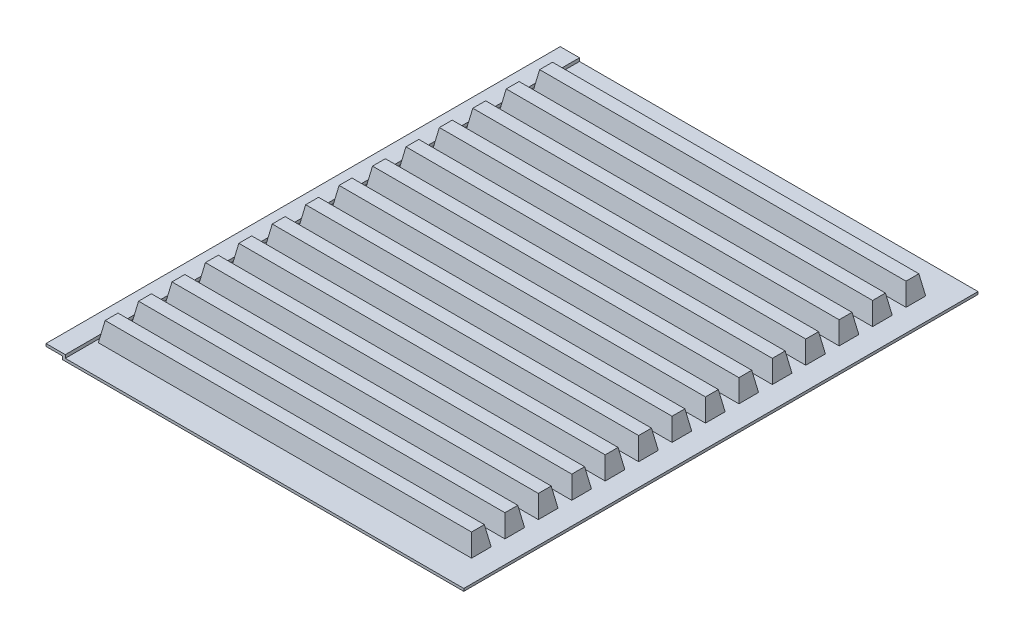
SolidWorks part; units mm, degrees
ref_plane "Front Plane" through (0, 0, 0) normal (0, 0, 1) x (1, 0, 0)
ref_plane "Top Plane" through (0, 0, 0) normal (0, 1, 0) x (1, 0, 0)
ref_plane "Right Plane" through (0, 0, 0) normal (1, 0, 0) x (0, 0, -1)
sketch "Sketch1" plane through (0, 0, 0) normal (0, 1, 0) x (1, 0, 0)
  line L1 (-206.375, 254) -> (206.375, 254)
  line L2 (-206.375, 254) -> (-206.375, -254)
  line L3 (-206.375, -254) -> (206.375, -254)
  line L4 (206.375, 254) -> (206.375, -254)
  line L5 (-206.375, 254) -> (206.375, -254) construction
  line L6 (-206.375, -254) -> (206.375, 254) construction
  point P0 (0, 0)
  dimension "D1" = 508
  dimension "D2" = 412.75
extrude "Boss-Extrude1" add sketch "Sketch1" along normal blind 2.54
sketch "Sketch2" plane through (0, 0, 0) normal (1, 0, 0) x (0, 0, -1)
  line L0 (-254, 2.54) -> (254, 2.54) construction
  line L1 (-208.28, 2.54) -> (-220.98, 2.54)
  line L2 (-208.28, 2.54) -> (-208.28, 21.59)
  line L3 (-208.28, 21.59) -> (-220.98, 21.59)
  line L4 (-220.98, 2.54) -> (-220.98, 21.59)
  line L5 (-214.63, 2.54) -> (-214.63, 21.59) construction
  dimension "D1" = 214.63
  dimension "D2" = 12.7
  dimension "D3" = 6.35
  dimension "D4" = 19.05
extrude "Boss-Extrude2" add sketch "Sketch2" along normal mid plane 361.95
draft "Draft2" type of draft neutral plane draft angle 10 faces to draft 4 face at (180.975, 12.065, 214.63) face at (0, 12.065, 220.98) face at (-180.975, 12.065, 214.63) face at (0, 12.065, 208.28) neutral plane through (180.975, 21.59, 208.28) neutral plane normal (0, 1, 0) parameters "D1"=10
pattern_linear "LPattern1" count 14 spacing 33.02 along (0, 0, -1) of "Boss-Extrude2", "Draft2"
sketch "Sketch3" plane through (0, 2.54, 0) normal (0, 1, 0) x (1, 0, 0)
  line L0 (-206.375, -254) -> (206.375, -254) construction
  line L1 (-206.375, 254) -> (-187.325, 254)
  line L2 (-206.375, 254) -> (-206.375, -254)
  line L3 (-206.375, -254) -> (-187.325, -254)
  line L4 (-187.325, 254) -> (-187.325, -254)
  dimension "D1" = 19.05
extrude "Boss-Extrude3" add sketch "Sketch3" along normal blind 3.175
shell "Shell10" thickness 2.54 removed face at (0, 0, 0) removed face at (-62.4417, 2.7517, 254) removed face at (-206.375, 2.8575, 0) removed face at (-62.4417, 2.7517, -254)
